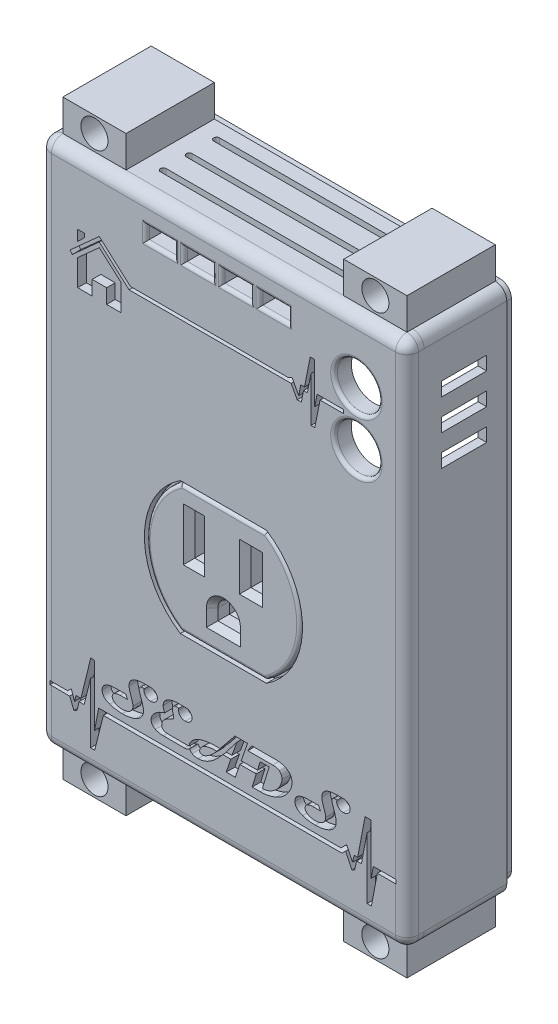
SolidWorks part; units mm, degrees
ref_plane "Front Plane" through (0, 0, 0) normal (0, 0, 1) x (1, 0, 0)
ref_plane "Top Plane" through (0, 0, 0) normal (0, 1, 0) x (1, 0, 0)
ref_plane "Right Plane" through (0, 0, 0) normal (1, 0, 0) x (0, 0, -1)
sketch "Sketch1" plane through (0, 0, 0) normal (0, 0, 1) x (1, 0, 0)
  line L0 (-40.64, -58.42) -> (40.64, -58.42)
  line L1 (-40.64, 58.42) -> (40.64, 58.42)
  line L2 (-40.64, 58.42) -> (-40.64, -58.42)
  line L3 (-40.64, -58.42) -> (40.64, -58.42) construction
  line L4 (40.64, 58.42) -> (40.64, -58.42)
  line L5 (-40.64, 58.42) -> (40.64, -58.42) construction
  line L6 (-40.64, -58.42) -> (40.64, 58.42) construction
  line L7 (-40.64, 58.42) -> (40.64, 58.42) construction
  line L9 (-40.64, 0) -> (40.64, 0) construction
  point P0 (0, 0)
sketch "Sketch4" plane through (0, 0, 0) normal (0, 0, 1) x (1, 0, 0)
  line L1 (-36.195, 56.515) -> (36.195, 56.515)
  line L2 (-38.735, 53.975) -> (-38.735, -53.975)
  line L3 (-36.195, -56.515) -> (36.195, -56.515)
  line L4 (38.735, 53.975) -> (38.735, -53.975)
  arc A0 (-38.735, 53.975) -> (-36.195, 56.515) centre (-36.195, 53.975) ccw
  arc A1 (36.195, 56.515) -> (38.735, 53.975) centre (36.195, 53.975) ccw
  arc A2 (-36.195, -56.515) -> (-38.735, -53.975) centre (-36.195, -53.975) ccw
  arc A3 (38.735, -53.975) -> (36.195, -56.515) centre (36.195, -53.975) ccw
  dimension "D1" = 5.08
sketch "Sketch5" plane through (0, 0, 0) normal (0, 0, 1) x (1, 0, 0)
  line L1 (-38.735, 53.975) -> (-38.735, 18.415) construction
  line L2 (38.735, 53.975) -> (38.735, 18.415) construction
  line L3 (-38.735, 18.415) -> (38.735, 18.415) construction
  line L4 (-25.4, 53.594) -> (-25.4, 56.515)
  line L6 (-25.4, 56.515) -> (-30.48, 56.515)
  line L7 (-30.48, 56.515) -> (-30.48, 53.594)
  line L8 (25.4, 53.594) -> (25.4, 56.515)
  line L9 (25.4, 56.515) -> (30.48, 56.515)
  line L10 (30.48, 56.515) -> (30.48, 53.594)
  line L11 (-35.56, 23.495) -> (-38.735, 23.495)
  line L12 (-38.735, 23.495) -> (-38.735, 18.415)
  line L13 (-38.735, 18.415) -> (-35.56, 18.415)
  line L14 (35.56, 23.495) -> (38.735, 23.114)
  line L15 (38.735, 23.114) -> (38.735, 18.415)
  line L16 (38.735, 18.415) -> (35.56, 18.415)
  arc A0 (-30.48, 53.594) -> (-25.4, 53.594) centre (-27.94, 53.594) ccw
  arc A1 (-35.56, 18.415) -> (-35.56, 23.495) centre (-35.56, 20.955) ccw
  arc A2 (25.4, 53.594) -> (30.48, 53.594) centre (27.94, 53.594) ccw
  arc A3 (35.56, 23.495) -> (35.56, 18.415) centre (35.56, 20.955) ccw
  dimension "D1" = 5.08
  dimension "D3" = 10.795
  dimension "D4" = 10.795
  dimension "D6" = 2.54
  dimension "D7" = 3.175
  dimension "D8" = 3.175
extrude "Case Extrude" add sketch "Sketch1" against normal blind 20.32
extrude "Case Cut" cut sketch "Sketch4" against normal blind 25.4
extrude "DaughterBoard Extrude" add sketch "Sketch5" against normal blind 9.525
sketch "Sketch6" plane through (0, 0, 0) normal (0, 0, 1) x (1, 0, 0)
  circle A0 centre (-27.94, 53.594) radius 0.9525
  circle A1 centre (-35.56, 20.955) radius 0.9525
  circle A2 centre (35.56, 20.955) radius 0.9525
  circle A3 centre (27.94, 53.594) radius 0.9525
  dimension "D1" = 1.905
extrude "DaughterBoard Holes" cut sketch "Sketch6" against normal blind 9.525
sketch "Sketch8" plane through (0, 0, 0) normal (0, 0, 1) x (1, 0, 0)
  circle A0 centre (-36.195, 53.975) radius 0.9525
  circle A1 centre (-36.195, -53.975) radius 0.9525
  circle A2 centre (36.195, 53.975) radius 0.9525
  circle A3 centre (36.195, -53.975) radius 0.9525
  dimension "D1" = 1.905
extrude "Cut-Extrude6" cut sketch "Sketch8" against normal through all
fillet "Fillet2" radius 2.54 1 edges at (40.64, 58.42, -10.16) type face fillet first side face at (40.64, 0, -10.16) second side face at (0, 58.42, -10.16)
fillet "Fillet3" radius 2.54 1 edges at (-40.64, 58.42, -10.16) type face fillet first side face at (-40.64, 0, -10.16) second side face at (-1.27, 58.42, -10.16)
fillet "Fillet4" radius 2.54 1 edges at (-40.64, -58.42, -10.16) type face fillet first side face at (-40.64, -1.27, -10.16) second side face at (0, -58.42, -10.16)
fillet "Fillet5" radius 2.54 1 edges at (40.64, -58.42, -10.16) type face fillet first side face at (1.27, -58.42, -10.16) second side face at (40.64, -1.27, -10.16)
ref_plane "Left Side Plane" through (-40.64, 0, 0) normal (-1, 0, 0) x (0, 0, 1)
sketch "Sketch11" plane through (-40.64, 0, 0) normal (-1, 0, 0) x (0, 0, 1)
  line L0 (-25.4, 33.3539) -> (-25.4, 27.7659)
  line L1 (-23.3153, 53.4199) -> (-2.9953, 53.4199) construction
  line L2 (-25.4, 21.6699) -> (-25.4, 16.0819)
  line L3 (-20.32, 55.88) -> (0, 55.88)
  line L4 (-11.43, 53.4199) -> (-11.43, 1.9849) construction
  line L6 (-22.0453, 17.3087) -> (-1.7253, 17.3087) construction
  line L7 (-22.8236, 33.3539) -> (-25.4, 33.3539)
  line L8 (-22.8236, 27.7659) -> (-25.4, 27.7659)
  line L9 (-17.5768, 35.4697) -> (-17.5768, 51.2722) construction
  line L10 (-25.4, 33.3539) -> (-25.4, 27.7659)
  line L11 (-22.8236, 21.6699) -> (-25.4, 21.6699)
  line L12 (-22.8236, 16.0819) -> (-25.4, 16.0819)
  arc A1 (-22.8236, 27.7659) -> (-22.8236, 33.3539) centre (-22.8236, 30.5599) ccw
  arc A2 (-22.8236, 16.0819) -> (-22.8236, 21.6699) centre (-22.8236, 18.8759) ccw
  circle A3 centre (-13.4493, 35.4697) radius 4.1275
  dimension "D1" = 5.588
  dimension "D6" = 8.255
  dimension "D3" = 22.86
  dimension "D5" = 11.684
  dimension "D8" = 18.161
  dimension "D9" = 6.1468
extrude "Cut-Extrude7" cut sketch "Sketch11" against normal blind 2.032 contours A3
chamfer "Chamfer1" distance 0.635 angle 45 1 edges at (-40.64, 35.4697, -9.3218)
chamfer "Chamfer2" distance 0.762 angle 45 1 edges at (-38.735, 31.3422, -13.4493)
ref_plane "Plane1" through (0, 0, -20.32) normal (0, 0, -1) x (-1, 0, 0)
sketch "Sketch12" plane through (0, 0, -20.32) normal (0, 0, -1) x (-1, 0, 0)
  line L0 (-40.64, -58.42) -> (40.64, -58.42)
  line L1 (-40.64, 58.42) -> (40.64, 58.42)
  line L2 (-40.64, 58.42) -> (-40.64, -58.42)
  line L3 (-40.64, -58.42) -> (40.64, -58.42) construction
  line L4 (40.64, 58.42) -> (40.64, -58.42)
  line L5 (-40.64, 58.42) -> (40.64, -58.42) construction
  line L6 (-40.64, -58.42) -> (40.64, 58.42) construction
  line L7 (-40.64, 58.42) -> (40.64, 58.42) construction
  line L8 (-39.624, 57.404) -> (39.624, 57.404)
  line L9 (-40.64, 0) -> (40.64, 0) construction
  line L10 (39.624, 57.404) -> (39.624, -57.404)
  line L11 (-39.624, -57.404) -> (39.624, -57.404)
  line L12 (-39.624, 57.404) -> (-39.624, -57.404)
  point P0 (0, 0)
  dimension "D1" = 1.016
extrude "Cut-Extrude9" cut sketch "Sketch12" against normal blind 2.032
fillet "Fillet7" radius 2.54 1 edges at (-39.624, 57.404, -19.304) type face fillet first side face at (-39.624, 0, -19.304) second side face at (0, 57.404, -19.304)
fillet "Fillet8" radius 2.54 1 edges at (-39.624, -57.404, -19.304) type face fillet first side face at (-39.624, -1.27, -19.304) second side face at (0, -57.404, -19.304)
fillet "Fillet9" radius 2.54 1 edges at (39.624, -57.404, -19.304) type face fillet first side face at (1.27, -57.404, -19.304) second side face at (39.624, 0, -19.304)
fillet "Fillet10" radius 2.54 1 edges at (39.624, 57.404, -19.304) type face fillet first side face at (39.624, 1.27, -19.304) second side face at (1.27, 57.404, -19.304)
ref_plane "Plane2" through (0, 58.42, 0) normal (0, 1, 0) x (1, 0, 0)
sketch "Sketch13" plane through (0, 58.42, 0) normal (0, 1, 0) x (1, 0, 0)
  line L0 (-19.9314, 2.8156) -> (21.8732, 2.8156) construction
  line L1 (-19.9314, 3.4506) -> (21.8732, 3.4506)
  line L2 (-19.9314, 2.1806) -> (21.8732, 2.1806)
  line L3 (-19.9314, 8.5538) -> (21.8732, 8.5538) construction
  line L4 (-19.9314, 9.1888) -> (21.8732, 9.1888)
  line L5 (-19.9314, 7.9188) -> (21.8732, 7.9188)
  line L6 (-19.9314, 14.6091) -> (21.8732, 14.6091) construction
  line L7 (-19.9314, 15.2441) -> (21.8732, 15.2441)
  line L8 (-19.9314, 13.9741) -> (21.8732, 13.9741)
  arc A0 (-19.9314, 3.4506) -> (-19.9314, 2.1806) centre (-19.9314, 2.8156) ccw
  arc A1 (21.8732, 2.1806) -> (21.8732, 3.4506) centre (21.8732, 2.8156) ccw
  arc A2 (-19.9314, 9.1888) -> (-19.9314, 7.9188) centre (-19.9314, 8.5538) ccw
  arc A3 (21.8732, 7.9188) -> (21.8732, 9.1888) centre (21.8732, 8.5538) ccw
  arc A4 (-19.9314, 15.2441) -> (-19.9314, 13.9741) centre (-19.9314, 14.6091) ccw
  arc A5 (21.8732, 13.9741) -> (21.8732, 15.2441) centre (21.8732, 14.6091) ccw
  point P2 (0.9709, 2.8156)
  point P7 (0.9709, 8.5538)
  point P14 (0.9709, 14.6091)
extrude "Cut-Extrude10" cut sketch "Sketch13" against normal through all
sketch "Sketch25" plane through (40.64, 0, 0) normal (1, 0, 0) x (0, 0, -1)
  line L0 (8.8181, 44.704) -> (8.8181, 40.894) construction
  line L1 (3.7987, 47.752) -> (13.8375, 47.752)
  line L2 (3.7987, 47.752) -> (3.7987, 44.704)
  line L3 (3.7987, 44.704) -> (13.8375, 44.704)
  line L4 (13.8375, 47.752) -> (13.8375, 44.704)
  line L5 (3.7987, 40.894) -> (13.8375, 40.894)
  line L6 (3.7987, 40.894) -> (3.7987, 37.846)
  line L7 (3.7987, 37.846) -> (13.8375, 37.846)
  line L8 (13.8375, 40.894) -> (13.8375, 37.846)
  line L9 (3.7987, 34.036) -> (13.8375, 34.036)
  line L10 (3.7987, 34.036) -> (3.7987, 30.988)
  line L11 (3.7987, 30.988) -> (13.8375, 30.988)
  line L12 (13.8375, 34.036) -> (13.8375, 30.988)
  line L13 (8.8181, 37.846) -> (8.8181, 34.036) construction
  line L14 (9.144, 55.88) -> (9.144, 47.752) construction
  line L15 (18.288, 55.88) -> (0, 55.88) construction
  dimension "D1" = 8.128
  dimension "D2" = 3.048
  dimension "D3" = 3.81
ref_plane "Plane3" through (0, 0, 0) normal (0, 0, 1) x (1, 0, 0)
sketch "Sketch14" plane through (0, 0, 0) normal (0, 0, 1) x (1, 0, 0)
  line L0 (-40.64, -58.42) -> (40.64, -58.42)
  line L1 (-40.64, 58.42) -> (40.64, 58.42)
  line L2 (-40.64, 58.42) -> (-40.64, -58.42)
  line L3 (-40.64, -58.42) -> (40.64, -58.42) construction
  line L4 (40.64, 58.42) -> (40.64, -58.42)
  line L5 (-40.64, 58.42) -> (40.64, -58.42) construction
  line L6 (-40.64, -58.42) -> (40.64, 58.42) construction
  line L7 (-40.64, 58.42) -> (40.64, 58.42) construction
  line L9 (-40.64, 0) -> (40.64, 0) construction
  point P0 (0, 0)
extrude "Boss-Extrude1" add sketch "Sketch14" along normal blind 3.81 separate body
sketch "Sketch15" plane through (0, 0, 0) normal (0, 0, 1) x (1, 0, 0)
  line L0 (2.794, 52.4985) -> (2.794, 49.4505) construction
  line L1 (-17.145, 52.4985) -> (-10.795, 52.4985)
  line L2 (-17.145, 52.4985) -> (-17.145, 49.4505)
  line L3 (-17.145, 49.4505) -> (-10.795, 49.4505)
  line L4 (-10.795, 52.4985) -> (-10.795, 49.4505)
  line L5 (-8.763, 52.4985) -> (-2.413, 52.4985)
  line L6 (-8.763, 52.4985) -> (-8.763, 49.4505)
  line L7 (-8.763, 49.4505) -> (-2.413, 49.4505)
  line L8 (-2.413, 52.4985) -> (-2.413, 49.4505)
  line L9 (-0.381, 52.4985) -> (5.969, 52.4985)
  line L10 (-0.381, 52.4985) -> (-0.381, 49.4505)
  line L11 (-0.381, 49.4505) -> (5.969, 49.4505)
  line L12 (5.969, 52.4985) -> (5.969, 49.4505)
  line L13 (8.001, 52.4985) -> (14.351, 52.4985)
  line L14 (8.001, 52.4985) -> (8.001, 49.4505)
  line L15 (8.001, 49.4505) -> (14.351, 49.4505)
  line L16 (14.351, 52.4985) -> (14.351, 49.4505)
  line L17 (-5.588, 52.4985) -> (-5.588, 49.4505) construction
  line L18 (-13.97, 52.4985) -> (-13.97, 49.4505) construction
  line L19 (-17.145, 50.9745) -> (-17.8007, 50.9745) construction
  line L21 (14.351, 50.9745) -> (15.0067, 50.9745) construction
  line L23 (-13.97, 52.4985) -> (-13.97, 56.515) construction
  line L29 (38.3068, 56.515) -> (-38.1, 56.515) construction
  line L34 (38.735, 53.975) -> (38.735, -51.7067) construction
  line L36 (11.176, 52.4985) -> (11.176, 49.4505) construction
  line L37 (8.001, 50.9745) -> (14.351, 50.9745) construction
  line L38 (-17.145, 50.9745) -> (-10.795, 50.9745) construction
  line L39 (-8.763, 50.9745) -> (-2.413, 50.9745) construction
  line L40 (-0.381, 50.9745) -> (5.969, 50.9745) construction
  line L43 (15.0067, 44.8251) -> (15.0067, 54.691) construction
  line L44 (-38.735, 53.975) -> (-38.735, 33.0818) construction
  circle A0 centre (29.464, 44.831) radius 4.953
  circle A1 centre (29.464, 32.893) radius 4.953
  dimension "D3" = 9.906
  dimension "D8" = 24.765
  dimension "D1" = 6.35
  dimension "D2" = 3.048
  dimension "D4" = 11.938
  dimension "D6" = 5.5405
  dimension "D7" = 9.271
  dimension "D11" = 8.382
  dimension "D12" = 8.382
  dimension "D13" = 8.382
extrude "Cut-Extrude11" cut sketch "Sketch15" along normal through all
sketch "Sketch16" plane through (0, 0, 0) normal (0, 0, 1) x (1, 0, 0)
  line L0 (-4.8133, -2.5527) -> (5.461, -2.5527) construction
  line L13 (-36.195, -51.435) -> (36.195, -51.435) construction
  line L14 (-2.4892, -14.097) -> (-2.4892, -16.5862)
  line L15 (-2.4892, -16.5862) -> (2.4892, -16.5862)
  line L16 (2.4892, -14.097) -> (2.4892, -16.5862)
  line L17 (-2.4892, -11.6078) -> (2.4892, -16.5862) construction
  line L18 (-2.4892, -16.5862) -> (2.5639, -11.5331) construction
  line L19 (7.62, -2.5527) -> (38.735, -2.5527) construction
  line L21 (-7.3533, -2.5527) -> (-38.735, -2.5527) construction
  line L23 (0, 58.42) -> (0, -58.42) construction
  line L26 (7.3533, 1.4478) -> (7.3533, -6.5532)
  line L27 (7.3533, -6.5532) -> (4.8133, -6.5532)
  line L28 (-5.461, 2.032) -> (-7.62, 2.032)
  line L29 (-5.461, 2.032) -> (-5.461, -7.1374)
  line L30 (-7.62, 2.032) -> (-7.62, -7.1374)
  line L31 (-5.461, -7.1374) -> (-7.62, -7.1374)
  line L32 (7.3533, 1.4478) -> (4.8133, 1.4478)
  line L33 (4.8133, 1.4478) -> (4.8133, -6.5532)
  arc A0 (2.4892, -14.097) -> (-2.4892, -14.097) centre (0, -14.097) ccw
  point P0 (-6.0833, -2.5527)
  point P5 (6.5405, -2.5527)
  point P10 (0, -14.097)
  dimension "D6" = 4.9784
  dimension "D5" = 12.6238
  dimension "D8" = 37.338
  dimension "D9" = 31.115
extrude "Cut-Extrude12" cut sketch "Sketch16" along normal through all
sketch "Sketch18" plane through (0, 0, 0) normal (0, 0, 1) x (1, 0, 0)
  line L0 (11.3395, 3.8087) -> (0.8271, 3.8087)
  line L1 (0.8271, -8.9141) -> (0.8271, 3.8087)
  line L2 (-7.62, -7.1374) -> (-5.461, 2.032) construction
  line L3 (-5.461, 2.032) -> (-7.62, 2.032) construction
  line L4 (-7.62, 2.032) -> (-5.461, -7.1374) construction
  line L5 (4.8133, 1.4478) -> (7.3533, -6.5532) construction
  line L6 (4.8133, -6.5532) -> (7.3533, 1.4478) construction
  line L7 (-11.6632, 3.8087) -> (-1.4178, 3.8087)
  line L8 (11.3395, -8.9141) -> (0.8271, -8.9141)
  line L9 (11.3395, -8.9141) -> (11.3395, 3.8087)
  line L10 (-4.9784, -14.097) -> (-4.9784, -19.0754)
  line L11 (-4.9784, -19.0754) -> (4.9784, -19.0754)
  line L12 (4.9784, -19.0754) -> (4.9784, -14.097)
  line L16 (-3.7084, -14.097) -> (-3.7084, -17.8054)
  line L17 (-3.7084, -17.8054) -> (3.7084, -17.8054)
  line L18 (3.7084, -17.8054) -> (3.7084, -14.097)
  line L30 (10.3235, -7.8981) -> (1.8431, -7.8981)
  line L31 (10.3235, -7.8981) -> (10.3235, 2.7927)
  line L32 (10.3235, 2.7927) -> (1.8431, 2.7927)
  line L33 (1.8431, -7.8981) -> (1.8431, 2.7927)
  line L34 (10.3235, -7.8981) -> (1.8431, 2.7927) construction
  line L35 (10.3235, 2.7927) -> (1.8431, -7.8981) construction
  line L36 (-10.6472, -7.8981) -> (-2.4338, -7.8981)
  line L41 (39.37, -57.15) -> (39.37, 57.15)
  line L42 (39.37, 57.15) -> (-39.37, 57.15)
  line L43 (-39.37, 57.15) -> (-39.37, -57.15)
  line L44 (-39.37, -57.15) -> (39.37, -57.15)
  line L45 (-10.6472, -7.8981) -> (-10.6472, 2.7927)
  line L46 (-10.6472, 2.7927) -> (-2.4338, 2.7927)
  line L47 (-2.4338, -7.8981) -> (-2.4338, 2.7927)
  line L48 (-10.6472, -7.8981) -> (-2.4338, 2.7927) construction
  line L49 (-10.6472, 2.7927) -> (-2.4338, -7.8981) construction
  line L50 (-1.4178, -8.9141) -> (-1.4178, 3.8087)
  line L51 (-11.6632, -8.9141) -> (-1.4178, -8.9141)
  line L52 (-11.6632, -8.9141) -> (-11.6632, 3.8087)
  arc A2 (4.9784, -14.097) -> (-4.9784, -14.097) centre (0, -14.097) ccw
  arc A4 (3.7084, -14.097) -> (-3.7084, -14.097) centre (0, -14.097) ccw
  point P30 (6.0833, -2.5527)
  point P35 (-6.5405, -2.5527)
  dimension "D2" = 1.27
  dimension "D4" = 1.016
  dimension "D5" = 1.016
extrude "Boss-Extrude2" add sketch "Sketch18" against normal blind 10.16 contours L12 A2 L10 L11 | A4 L16 L17 L18 | L50 L7 L52 L51 | L47 L46 L45 L36 | L32 L33 L30 L31 | L0 L1 L8 L9
ref_plane "Plane4" through (0, 0, 3.81) normal (0, 0, 1) x (1, 0, 0)
sketch "Sketch19" plane through (0, 0, 0) normal (0, 0, 1) x (1, 0, 0)
  line L0 (2.794, 52.4985) -> (2.794, 49.4505) construction
  line L17 (-5.588, 52.4985) -> (-5.588, 49.4505) construction
  line L18 (-13.97, 52.4985) -> (-13.97, 49.4505) construction
  line L19 (-17.145, 50.9745) -> (-17.8007, 50.9745) construction
  line L20 (7.493, 53.0065) -> (14.859, 53.0065)
  line L21 (14.351, 50.9745) -> (15.0067, 50.9745) construction
  line L22 (14.859, 53.0065) -> (14.859, 48.9425)
  line L23 (-13.97, 52.4985) -> (-13.97, 56.515) construction
  line L24 (7.493, 48.9425) -> (14.859, 48.9425)
  line L25 (7.493, 53.0065) -> (7.493, 48.9425)
  line L26 (-0.889, 53.0065) -> (6.477, 53.0065)
  line L27 (6.477, 53.0065) -> (6.477, 48.9425)
  line L28 (-0.889, 48.9425) -> (6.477, 48.9425)
  line L29 (38.3068, 56.515) -> (-38.1, 56.515) construction
  line L30 (-0.889, 53.0065) -> (-0.889, 48.9425)
  line L31 (-9.271, 53.0065) -> (-1.905, 53.0065)
  line L32 (-1.905, 53.0065) -> (-1.905, 48.9425)
  line L33 (-9.271, 48.9425) -> (-1.905, 48.9425)
  line L34 (38.735, 53.975) -> (38.735, -51.7067) construction
  line L35 (-9.271, 53.0065) -> (-9.271, 48.9425)
  line L36 (11.176, 52.4985) -> (11.176, 49.4505) construction
  line L37 (8.001, 50.9745) -> (14.351, 50.9745) construction
  line L38 (-17.145, 50.9745) -> (-10.795, 50.9745) construction
  line L39 (-8.763, 50.9745) -> (-2.413, 50.9745) construction
  line L40 (-0.381, 50.9745) -> (5.969, 50.9745) construction
  line L41 (-17.653, 53.0065) -> (-10.287, 53.0065)
  line L42 (-10.287, 53.0065) -> (-10.287, 48.9425)
  line L43 (15.0067, 44.8251) -> (15.0067, 54.691) construction
  line L44 (-38.735, 53.975) -> (-38.735, 33.0818) construction
  line L45 (-17.653, 48.9425) -> (-10.287, 48.9425)
  line L46 (-17.653, 53.0065) -> (-17.653, 48.9425)
  line L47 (7.112, 53.3875) -> (7.112, 48.5615)
  line L48 (7.112, 48.5615) -> (15.24, 48.5615)
  line L49 (15.24, 53.3875) -> (15.24, 48.5615)
  line L50 (7.112, 53.3875) -> (15.24, 53.3875)
  line L51 (-1.27, 53.3875) -> (-1.27, 48.5615)
  line L52 (-1.27, 48.5615) -> (6.858, 48.5615)
  line L53 (6.858, 53.3875) -> (6.858, 48.5615)
  line L54 (-1.27, 53.3875) -> (6.858, 53.3875)
  line L55 (-9.652, 53.3875) -> (-9.652, 48.5615)
  line L56 (-9.652, 48.5615) -> (-1.524, 48.5615)
  line L57 (-1.524, 53.3875) -> (-1.524, 48.5615)
  line L58 (-9.652, 53.3875) -> (-1.524, 53.3875)
  line L59 (-18.034, 53.3875) -> (-18.034, 48.5615)
  line L60 (-18.034, 48.5615) -> (-9.906, 48.5615)
  line L61 (-9.906, 53.3875) -> (-9.906, 48.5615)
  line L62 (-18.034, 53.3875) -> (-9.906, 53.3875)
  dimension "D8" = 24.765
  dimension "D6" = 5.5405
  dimension "D9" = 0.381
  dimension "D11" = 8.382
  dimension "D12" = 8.382
  dimension "D13" = 8.382
extrude "Boss-Extrude3" add sketch "Sketch19" against normal blind 2.54
fillet "Fillet11" radius 2.54 4 edges at (40.64, -58.42, 1.905) (-40.64, -58.42, 1.905) (-40.64, 58.42, 1.905) (40.64, 58.42, 1.905)
fillet "Fillet12" radius 0.762 18 edges at (-17.145, 50.9745, 3.81) (-13.97, 49.4505, 3.81) (-13.97, 52.4985, 3.81) (-10.795, 50.9745, 3.81) (-8.763, 50.9745, 3.81) (-5.588, 49.4505, 3.81) (-5.588, 52.4985, 3.81) (-2.413, 50.9745, 3.81) (-0.381, 50.9745, 3.81) (2.794, 52.4985, 3.81) (5.969, 50.9745, 3.81) (2.794, 49.4505, 3.81) (8.001, 50.9745, 3.81) (11.176, 52.4985, 3.81) (14.351, 50.9745, 3.81) (11.176, 49.4505, 3.81) (34.417, 32.893, 3.81) (34.417, 44.831, 3.81)
chamfer "Chamfer3" distance 1.27 angle 45 12 edges at (-6.5405, -7.1374, 3.81) (-7.62, -2.5527, 3.81) (-6.5405, 2.032, 3.81) (-5.461, -2.5527, 3.81) (0, -16.5862, 3.81) (2.4892, -15.3416, 3.81) (-2.4892, -15.3416, 3.81) (0, -11.6078, 3.81) (6.0833, -6.5532, 3.81) (4.8133, -2.5527, 3.81) (6.0833, 1.4478, 3.81) (7.3533, -2.5527, 3.81)
sketch "Sketch20" plane through (0, 0, 3.81) normal (0, 0, 1) x (1, 0, 0)
  line L0 (-9.398, 6.9088) -> (9.398, 6.9088)
  line L1 (-9.398, -21.4122) -> (9.398, -21.4122)
  line L2 (-9.55, -21.9202) -> (9.55, -21.9202)
  line L3 (-9.55, 7.4168) -> (9.55, 7.4168)
  line L4 (-7.62, 2.032) -> (-5.461, 2.032) construction
  line L5 (-2.4384, -16.5354) -> (2.4384, -16.5354) construction
  line L6 (-6.5405, 2.032) -> (-6.5405, 6.9088) construction
  line L7 (0, -16.5354) -> (0, -21.4122) construction
  line L8 (0, -7.2517) -> (16.9954, -7.2517) construction
  line L14 (0, -7.2517) -> (-16.9954, -7.2517) construction
  arc A0 (-9.398, 6.9088) -> (-9.398, -21.4122) centre (0, -7.2517) ccw
  arc A1 (-9.55, 7.4168) -> (-9.55, -21.9202) centre (0, -7.2517) ccw
  arc A2 (9.398, -21.4122) -> (9.398, 6.9088) centre (0, -7.2517) ccw
  arc A3 (9.55, -21.9202) -> (9.55, 7.4168) centre (0, -7.2517) ccw
  dimension "D1" = 0.508
  dimension "D2" = 28.321
  dimension "D3" = 0.508
  dimension "D4" = 0.508
  dimension "D5" = 18.796
extrude "Cut-Extrude13" cut sketch "Sketch20" against normal blind 1.905 contours A1 L2 A3 L3 | A0 L1 A2 L0
fillet "Fillet13" radius 0.762 4 edges at (16.9954, -7.2517, 3.81) (0, 6.9088, 3.81) (0, -21.4122, 3.81) (-16.9954, -7.2517, 3.81)
fillet "Fillet14" radius 2.54 8 edges at (0, -58.42, 3.81) (-39.8961, -57.6761, 3.81) (-40.64, 0, 3.81) (-39.8961, 57.6761, 3.81) (0, 58.42, 3.81) (39.8961, 57.6761, 3.81) (39.8961, -57.6761, 3.81) (40.64, 0, 3.81)
sketch "Sketch21" plane through (0, 0, 3.81) normal (0, 0, 1) x (1, 0, 0)
  line L0 (-32.2727, 38.8156) -> (-32.2727, 33.0329)
  line L1 (-32.2727, 33.0329) -> (-29.0668, 33.0329)
  line L2 (-29.0668, 33.0329) -> (-29.0668, 36.2389)
  line L3 (-29.0668, 36.2389) -> (-25.8608, 36.2389)
  line L4 (-25.8608, 36.2389) -> (-25.8608, 33.0329)
  line L5 (-25.8608, 33.0329) -> (-22.6549, 33.0329)
  line L6 (-22.6549, 33.0329) -> (-22.6549, 38.8156)
  line L7 (-22.6549, 38.8156) -> (-27.4959, 43.1116)
  line L8 (-27.4959, 43.1116) -> (-32.2727, 38.8156)
  line L9 (-32.2727, 44.2368) -> (-32.2727, 41.8876)
  line L10 (-32.2727, 41.8876) -> (-30.7668, 43.3935)
  line L11 (-30.7668, 43.3935) -> (-30.7668, 44.2368)
  line L12 (-30.7668, 44.2368) -> (-32.2727, 44.2368)
  line L13 (-33.4695, 38.8068) -> (-27.4994, 44.1759)
  line L14 (-27.4994, 44.1759) -> (-20.9009, 38.3203)
  line L15 (-20.9009, 38.3203) -> (14.9947, 38.3203)
  line L17 (14.9947, 38.3203) -> (16.3406, 35.8462)
  line L18 (16.3406, 35.8462) -> (17.2442, 35.8462)
  line L19 (17.2442, 35.8462) -> (17.7368, 38.3203)
  line L20 (17.7368, 38.3203) -> (18.5861, 38.3203)
  line L21 (18.5861, 38.3203) -> (19.3988, 42.4016)
  line L22 (19.3988, 42.4016) -> (19.3988, 32.4626)
  line L23 (19.3988, 32.4626) -> (20.2305, 32.4626)
  line L24 (20.2305, 32.4626) -> (21.3969, 38.3203)
  line L25 (21.3969, 39.1178) -> (20.7481, 39.1178)
  line L26 (20.7481, 39.1178) -> (20.2183, 36.4569)
  line L27 (20.2183, 36.4569) -> (20.2183, 45.4974)
  line L28 (20.2183, 45.4974) -> (19.216, 45.4974)
  line L29 (19.216, 45.4974) -> (17.9457, 39.1178)
  line L30 (17.9457, 39.1178) -> (17.1158, 39.1178)
  line L31 (17.1158, 39.1178) -> (16.6796, 36.8151)
  line L32 (16.6796, 36.8151) -> (15.1974, 39.5397)
  line L33 (15.1974, 39.5397) -> (14.422, 39.1178)
  line L34 (14.422, 39.1178) -> (-20.6038, 39.1178)
  line L35 (-20.6038, 39.1178) -> (-27.5029, 45.2403)
  line L36 (-27.5029, 45.2403) -> (-34.0003, 39.397)
  line L37 (-34.0003, 39.397) -> (-33.4695, 38.8068)
  line L38 (21.3969, 39.1178) -> (26.6217, 39.1178)
  line L39 (26.6217, 39.1178) -> (26.6217, 38.3203)
  line L40 (26.6217, 38.3203) -> (21.3969, 38.3203)
extrude "Cut-Extrude14" cut sketch "Sketch21" against normal blind 1.905
sketch "Sketch22" plane through (0, 0, 3.81) normal (0, 0, 1) x (1, 0, 0)
  line L0 (-38.4164, -46.1613) -> (-34.0454, -46.1613)
  line L2 (-34.0454, -46.1613) -> (-33.1049, -48.4372)
  line L3 (-33.1049, -48.4372) -> (-32.4401, -48.1547)
  line L4 (-32.4401, -48.1547) -> (-31.951, -46.1888)
  line L5 (-31.951, -46.1888) -> (-30.8399, -46.1888)
  line L6 (-30.8399, -46.1888) -> (-29.4169, -40.4413)
  line L7 (-29.4169, -40.4413) -> (-29.4169, -53.763)
  line L8 (-29.4169, -53.763) -> (-28.5099, -53.763)
  line L9 (-28.5099, -53.763) -> (-26.5889, -46.1368)
  line L10 (-26.5889, -46.1368) -> (26.2603, -46.1368)
  line L11 (26.2603, -46.1368) -> (27.0615, -45.3433)
  line L12 (27.0615, -45.3433) -> (28.4578, -48.2483)
  line L13 (28.4578, -48.2483) -> (29.0403, -47.9683)
  line L14 (29.0403, -47.9683) -> (29.4865, -46.0196)
  line L15 (29.4865, -46.0196) -> (30.5525, -46.0196)
  line L16 (30.5525, -46.0196) -> (31.8017, -39.4554)
  line L17 (31.8017, -39.4554) -> (31.8017, -53.0245)
  line L18 (31.8017, -53.0245) -> (32.758, -53.0245)
  line L19 (32.758, -53.0245) -> (34.0812, -46.0714)
  line L20 (34.0812, -46.0714) -> (38.2177, -46.0714)
  line L21 (38.2177, -46.0714) -> (38.2177, -45.1957)
  line L22 (38.2177, -45.1957) -> (33.1949, -45.1957)
  line L23 (33.1949, -45.1957) -> (32.7105, -47.7414)
  line L24 (32.7105, -47.7414) -> (32.7105, -36.5707)
  line L25 (32.7105, -36.5707) -> (31.3621, -36.5707)
  line L26 (31.3621, -36.5707) -> (29.7207, -45.1961)
  line L27 (29.7207, -45.1961) -> (28.9407, -45.1961)
  line L28 (28.9407, -45.1961) -> (28.595, -46.706)
  line L29 (28.595, -46.706) -> (27.7473, -44.9425)
  line L30 (27.7473, -44.9425) -> (27.2832, -43.9768)
  line L31 (27.2832, -43.9768) -> (26.0122, -45.2478)
  line L32 (26.0122, -45.2478) -> (-27.6326, -45.2478)
  line L33 (-27.6326, -45.2478) -> (-28.5388, -50.0096)
  line L34 (-28.5388, -50.0096) -> (-28.5388, -36.6051)
  line L35 (-28.5388, -36.6051) -> (-29.3569, -36.4494)
  line L36 (-29.3569, -36.4494) -> (-31.5613, -45.3531)
  line L37 (-31.5613, -45.3531) -> (-32.6569, -45.3531)
  line L38 (-32.6569, -45.3531) -> (-32.9846, -46.683)
  line L39 (-32.9846, -46.683) -> (-33.6806, -44.5701)
  line L41 (-33.6806, -44.5701) -> (-34.4729, -45.3624)
  line L42 (-34.4729, -45.3624) -> (-38.4164, -45.3624)
  line L43 (-38.4164, -45.3624) -> (-38.4164, -46.1613)
extrude "Cut-Extrude15" cut sketch "Sketch22" against normal blind 1.905
sketch "Sketch24" plane through (0, 0, 3.81) normal (0, 0, 1) x (1, 0, 0)
  text T0 "SEADS" font "Magneto" height in points 28
extrude "Cut-Extrude16" cut sketch "Sketch24" against normal blind 1.905
extrude "Cut-Extrude17" cut sketch "Sketch25" against normal up to surface (1.905 mm away) up to face at (38.735, 10.3823, -7.4612)
sketch "Sketch26" plane through (0, 58.42, 0) normal (0, 1, 0) x (1, 0, 0)
  line L0 (-38.1, -1.27) -> (38.1, -1.27) construction
  line L1 (-38.1, 18.288) -> (-24.1, 18.288)
  line L2 (-38.1, 18.288) -> (-38.1, -1.27)
  line L3 (-38.1, -1.27) -> (-24.1, -1.27)
  line L4 (-24.1, 18.288) -> (-24.1, -1.27)
  line L6 (38.1, 18.288) -> (24.1, 18.288)
  line L7 (38.1, 18.288) -> (38.1, -1.27)
  line L8 (38.1, -1.27) -> (24.1, -1.27)
  line L9 (24.1, 18.288) -> (24.1, -1.27)
  dimension "D1" = 14
sketch "Sketch27" plane through (0, -58.42, 0) normal (0, -1, 0) x (1, 0, 0)
  line L0 (38.1, 1.27) -> (-38.1, 1.27) construction
  line L1 (-38.1, -18.288) -> (-24.1, -18.288)
  line L2 (-38.1, -18.288) -> (-38.1, 1.27)
  line L3 (-38.1, 1.27) -> (-24.1, 1.27)
  line L4 (-24.1, -18.288) -> (-24.1, 1.27)
  line L6 (38.1, -18.288) -> (24.1, -18.288)
  line L7 (38.1, -18.288) -> (38.1, 1.27)
  line L8 (38.1, 1.27) -> (24.1, 1.27)
  line L9 (24.1, -18.288) -> (24.1, 1.27)
  dimension "D1" = 14
extrude "Boss-Extrude4" add sketch "Sketch26" along normal blind 7
extrude "Boss-Extrude5" add sketch "Sketch27" along normal blind 7
sketch "Sketch28" plane through (0, 0, -18.288) normal (0, 0, -1) x (-1, 0, 0)
  circle A0 centre (-31.1, 61.92) radius 1.575
  circle A1 centre (31.1, 61.92) radius 1.575
  circle A2 centre (31.1, -61.92) radius 1.575
  circle A3 centre (-31.1, -61.92) radius 1.575
  dimension "D1" = 3.15
extrude "Cut-Extrude18" cut sketch "Sketch28" along direction (0, 0, -1) on the side against the normal up to surface (19.558 mm away) up to face at (31.1, -61.92, 1.27)
sketch "Sketch31" plane through (0, 0, 1.27) normal (0, 0, 1) x (1, 0, 0)
  circle A0 centre (31.1, 61.92) radius 3
  circle A1 centre (-31.1, 61.92) radius 3
  circle A2 centre (-31.1, -61.92) radius 3
  circle A3 centre (31.1, -61.92) radius 3
  dimension "D1" = 6
extrude "Cut-Extrude19" cut sketch "Sketch31" against normal blind 8
